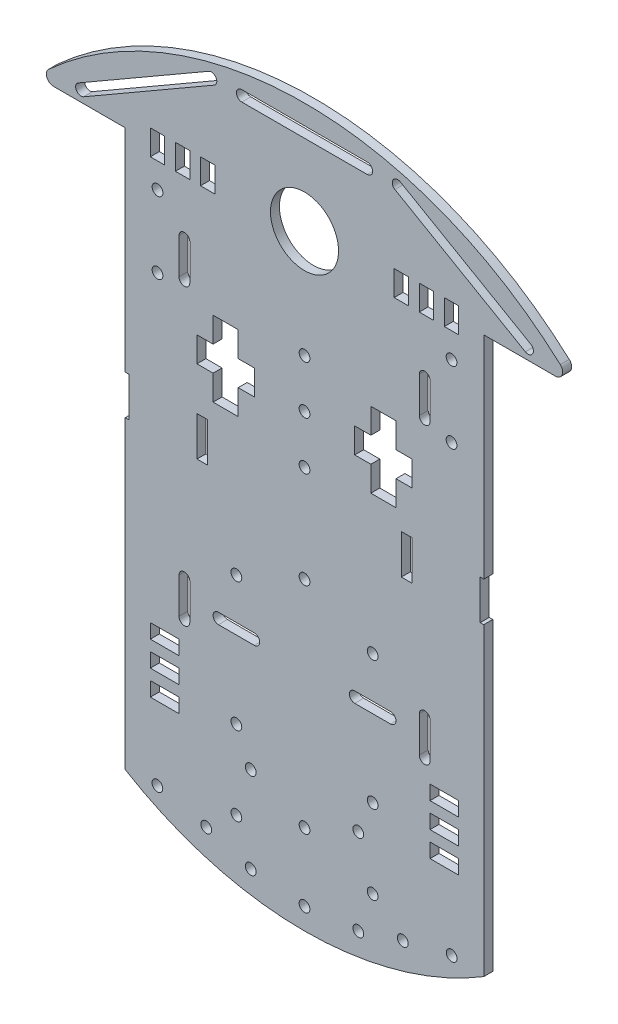
SolidWorks part; units mm, degrees
material "Acrylique (impact moyen-haut)"
ref_plane "Plan de face" through (0, 0, 0) normal (0, 0, 1) x (1, 0, 0)
ref_plane "Plan de dessus" through (0, 0, 0) normal (0, 1, 0) x (1, 0, 0)
ref_plane "Plan de droite" through (0, 0, 0) normal (1, 0, 0) x (0, 0, -1)
sketch "Esquisse1" plane through (0, 0, 0) normal (0, 0, 1) x (1, 0, 0)
  line L0 (100, 155) -> (119.9942, 155)
  line L1 (100, 77.5) -> (0, 77.5) construction
  line L2 (0, 0) -> (0, 155)
  line L3 (0, 155) -> (-19.9942, 155)
  line L4 (100, 0) -> (100, 155)
  line L5 (125, 155) -> (-25, 155) construction
  line L6 (125, 186) -> (-25, 186) construction
  line L7 (50, -14) -> (169.1274, -14) construction
  line L8 (50, 155) -> (50, 123.7315) construction
  arc A0 (121.3374, 158.4819) -> (-21.3374, 158.4819) centre (50, 79.7742) ccw
  arc A1 (100, 0) -> (0, 0) centre (50, 82.2857) cw
  arc A2 (-21.3374, 158.4819) -> (-19.9942, 155) centre (-19.9942, 157) ccw
  arc A3 (119.9942, 155) -> (121.3374, 158.4819) centre (119.9942, 157) ccw
  dimension "D3" = 200
  dimension "D5" = 31
  dimension "D1" = 2
  dimension "D2" = 100
  dimension "D4" = 150
  dimension "D6" = 155
extrude "Boss.-Extru.1" add sketch "Esquisse1" along normal blind 2.5 contours L4 L0 A3 A0 A2 L3 L2 A1
sketch "Esquisse2" plane through (0, 0, 0) normal (0, 0, -1) x (-1, 0, 0)
  line L0 (-100, 155) -> (0, 155) construction
  line L1 (-50, 155) -> (-50, 122.9953) construction
  circle A0 centre (-50, 155) radius 9.5
  point P6 (-50, 155)
  dimension "D1" = 19
extrude "Enlèv. mat.-Extru.1" cut sketch "Esquisse2" against normal through all
sketch "Esquisse3" plane through (0, 0, 0) normal (0, 0, -1) x (-1, 0, 0)
  line L1 (-93, 158.5) -> (-89, 158.5)
  line L2 (-93, 158.5) -> (-93, 151.5)
  line L3 (-93, 151.5) -> (-89, 151.5)
  line L4 (-89, 158.5) -> (-89, 151.5)
  line L5 (-100, 0) -> (-100, 155) construction
  line L11 (-100, 155) -> (-88.6993, 155) construction
  point P8 (-93, 155)
  dimension "D1" = 7
  dimension "D2" = 4
  dimension "D3" = 7
extrude "Enlèv. mat.-Extru.2" cut sketch "Esquisse3" against normal through all
pattern_linear "Répétition linéaire1" count 3 spacing 7 along (-1, 0, 0) of "Enlèv. mat.-Extru.2"
sketch "Esquisse4" plane through (0, 0, 0) normal (0, 0, -1) x (-1, 0, 0)
  line L0 (-75.5, 122) -> (-68.5, 122)
  line L1 (-68.5, 122) -> (-68.5, 115)
  line L2 (-68.5, 115) -> (-64, 115)
  line L3 (-64, 115) -> (-64, 108)
  line L4 (-64, 108) -> (-68.5, 108)
  line L5 (-68.5, 108) -> (-68.5, 101)
  line L6 (-68.5, 101) -> (-75.5, 101)
  line L7 (-75.5, 101) -> (-75.5, 108)
  line L8 (-75.5, 108) -> (-80, 108)
  line L9 (-80, 108) -> (-80, 115)
  line L10 (-80, 115) -> (-75.5, 115)
  line L11 (-75.5, 115) -> (-75.5, 122)
  line L12 (-100, 155) -> (-119.9942, 155) construction
  line L13 (-72, 122) -> (-72, 101) construction
  line L14 (-80, 111.5) -> (-64, 111.5) construction
  line L15 (-100, 0) -> (-100, 155) construction
  point P19 (-72, 111.5)
  point P21 (-72, 111.5)
  dimension "D1" = 47
  dimension "D2" = 7
  dimension "D3" = 16
  dimension "D4" = 21
  dimension "D5" = 7
  dimension "D6" = 20
extrude "Enlèv. mat.-Extru.3" cut sketch "Esquisse4" against normal through all
sketch "Esquisse5" plane through (0, 0, 0) normal (0, 0, -1) x (-1, 0, 0)
  line L0 (-80, 108) -> (-75.5, 108) construction
  line L1 (-80, 96) -> (-77, 96)
  line L2 (-80, 96) -> (-80, 85)
  line L3 (-80, 85) -> (-77, 85)
  line L4 (-77, 96) -> (-77, 85)
  line L5 (-100, 0) -> (-100, 155) construction
  dimension "D1" = 12
  dimension "D2" = 3
  dimension "D3" = 11
  dimension "D4" = 20
extrude "Enlèv. mat.-Extru.4" cut sketch "Esquisse5" against normal through all
pattern_linear "Répétition linéaire2" count 2 spacing 22 along (1, 0, 0) of "Enlèv. mat.-Extru.4"
sketch "Esquisse6" plane through (0, 0, 0) normal (0, 0, -1) x (-1, 0, 0)
  line L0 (-65, 17.5) -> (-65, 7.0648) construction
  line L1 (-100, 0) -> (-100, 85) construction
  line L2 (-83.5, 54.5) -> (-83.5, 44.5) construction
  line L3 (-82, 54.5) -> (-82, 44.5)
  line L4 (-85, 54.5) -> (-85, 44.5)
  line L5 (-74, 49.5) -> (-64, 49.5) construction
  line L6 (-74, 51) -> (-64, 51)
  line L7 (-74, 48) -> (-64, 48)
  line L8 (-83.5, 136.5) -> (-83.5, 126.5) construction
  line L9 (-82, 136.5) -> (-82, 126.5)
  line L10 (-85, 136.5) -> (-85, 126.5)
  line L11 (-112.3374, 158) -> (-75.9643, 179) construction
  line L12 (-113.0874, 159.299) -> (-76.7143, 180.299)
  line L13 (-111.5874, 156.701) -> (-75.2143, 177.701)
  line L14 (-112.3374, 158) -> (-68.1921, 158) construction
  line L15 (-100, 155) -> (-119.9942, 155) construction
  line L16 (-91, 151.5) -> (-91, 144.5) construction
  line L17 (-93, 151.5) -> (-89, 151.5) construction
  line L19 (-69, 49.5) -> (-69, 65.1561) construction
  line L20 (-50, 89.2969) -> (-50, -6.5) construction
  line L21 (0, 0) -> (0, 155) construction
  circle A0 centre (-91, 144.5) radius 1.5
  arc A1 (-82, 54.5) -> (-85, 54.5) centre (-83.5, 54.5) ccw
  circle A2 centre (-91, 124.5) radius 1.5
  circle A3 centre (-65, 17.5) radius 1.5
  circle A4 centre (-69, 26.5) radius 1.5
  circle A5 centre (-91.03, 0.6026) radius 1.5
  circle A6 centre (-77.4014, -2.6005) radius 1.5
  circle A7 centre (-69, 4.5) radius 1.5
  circle A8 centre (-65, -6.5) radius 1.5
  arc A9 (-85, 44.5) -> (-82, 44.5) centre (-83.5, 44.5) ccw
  arc A10 (-74, 51) -> (-74, 48) centre (-74, 49.5) ccw
  arc A11 (-64, 48) -> (-64, 51) centre (-64, 49.5) ccw
  arc A12 (-82, 136.5) -> (-85, 136.5) centre (-83.5, 136.5) ccw
  arc A13 (-85, 126.5) -> (-82, 126.5) centre (-83.5, 126.5) ccw
  arc A14 (-113.0874, 159.299) -> (-111.5874, 156.701) centre (-112.3374, 158) ccw
  arc A15 (-75.2143, 177.701) -> (-76.7143, 180.299) centre (-75.9643, 179) ccw
  circle A16 centre (-69, 62.5) radius 1.5
  point P21 (-83.5, 49.5)
  point P26 (-69, 49.5)
  point P33 (-83.5, 131.5)
  point P40 (-94.1508, 168.5)
  dimension "D1" = 3
  dimension "D2" = 3
  dimension "D3" = 3
  dimension "D4" = 3
  dimension "D5" = 3
  dimension "D6" = 3
  dimension "D7" = 3
  dimension "D10" = 3
  dimension "D11" = 3
  dimension "D28" = 3
  dimension "D8" = 24
  dimension "D9" = 15
  dimension "D12" = 3
  dimension "D13" = 3
  dimension "D14" = 3
  dimension "D15" = 15
  dimension "D16" = 8
  dimension "D17" = 10
  dimension "D18" = 10
  dimension "D19" = 10
  dimension "D20" = 42
  dimension "D21" = 3
  dimension "D22" = 9
  dimension "D23" = 30
  dimension "D24" = 7
  dimension "D25" = 15
  dimension "D26" = 20
  dimension "D27" = 72
  dimension "D29" = 11.5
  dimension "D30" = 21.5
  dimension "D31" = 137.5
  dimension "D32" = 14
  dimension "D33" = 13
  dimension "D34" = 11
  dimension "D35" = 22
  dimension "D36" = 34
extrude "Enlèv. mat.-Extru.5" cut sketch "Esquisse6" against normal through all
sketch "Esquisse7" plane through (0, 0, 0) normal (0, 0, -1) x (-1, 0, 0)
  line L0 (-100, 0) -> (-100, 85) construction
  line L5 (-93, 39) -> (-85, 39)
  line L6 (-93, 39) -> (-93, 35)
  line L7 (-93, 35) -> (-85, 35)
  line L8 (-85, 39) -> (-85, 35)
  line L9 (-93, 32) -> (-85, 32)
  line L10 (-93, 32) -> (-93, 28)
  line L11 (-93, 28) -> (-85, 28)
  line L12 (-85, 32) -> (-85, 28)
  line L13 (-93, 25) -> (-85, 25)
  line L14 (-93, 25) -> (-93, 21)
  line L15 (-93, 21) -> (-85, 21)
  line L16 (-85, 25) -> (-85, 21)
  arc A0 (-100, 0) -> (0, 0) centre (-50, 82.2857) ccw construction
  point P18 (-50, -14)
  dimension "D1" = 4
  dimension "D2" = 4
  dimension "D3" = 4
  dimension "D4" = 8
  dimension "D5" = 7
  dimension "D6" = 3
  dimension "D7" = 3
  dimension "D8" = 35
extrude "Enlèv. mat.-Extru.6" cut sketch "Esquisse7" against normal through all
ref_plane "Plan1" through (50, 0, 0) normal (1, 0, 0) x (0, 0, -1)
mirror "Symétrie1" about plane through (50, 0, 0) normal (1, 0, 0) of "Répétition linéaire2", "Enlèv. mat.-Extru.2", "Répétition linéaire1", "Enlèv. mat.-Extru.3", "Enlèv. mat.-Extru.4", "Enlèv. mat.-Extru.5", "Enlèv. mat.-Extru.6"
sketch "Esquisse8" plane through (0, 0, 0) normal (0, 0, -1) x (-1, 0, 0)
  line L0 (-67.5, 178.9806) -> (-32.5, 178.9806) construction
  line L1 (-67.5, 180.4806) -> (-32.5, 180.4806)
  line L2 (-67.5, 177.4806) -> (-32.5, 177.4806)
  line L5 (-50, 251.8346) -> (-50, 106.1266) construction
  line L6 (0, 0) -> (0, 85) construction
  line L7 (-100, 96) -> (-100, 155) construction
  line L8 (-64, 111.5) -> (-36, 111.5) construction
  line L9 (-64, 108) -> (-64, 115) construction
  line L10 (-36, 108) -> (-36, 115) construction
  arc A0 (-67.5, 180.4806) -> (-67.5, 177.4806) centre (-67.5, 178.9806) ccw
  arc A1 (-32.5, 177.4806) -> (-32.5, 180.4806) centre (-32.5, 178.9806) ccw
  circle A2 centre (-50, 111.5) radius 1.5
  circle A3 centre (-50, 125) radius 1.5
  circle A4 centre (-50, 98) radius 1.5
  circle A5 centre (-50, 71) radius 1.5
  circle A6 centre (-50, -8) radius 1.5
  circle A7 centre (-50, 11) radius 1.5
  point P2 (-50, 178.9806)
  dimension "D3" = 3
  dimension "D4" = 3
  dimension "D5" = 3
  dimension "D6" = 3
  dimension "D7" = 3
  dimension "D11" = 3
  dimension "D1" = 3
  dimension "D2" = 35
  dimension "D8" = 13.5
  dimension "D9" = 13.5
  dimension "D10" = 27
  dimension "D12" = 60
  dimension "D13" = 19
extrude "Enlèv. mat.-Extru.7" cut sketch "Esquisse8" against normal blind 10
equation "\"D2@Esquisse6\"=\"D1@Esquisse6\""
equation "\"D3@Esquisse6\"=\"D2@Esquisse6\""
equation "\"D4@Esquisse6\"=\"D2@Esquisse6\""
equation "\"D5@Esquisse6\"=\"D2@Esquisse6\""
equation "\"D6@Esquisse6\"=\"D2@Esquisse6\""
equation "\"D7@Esquisse6\"=\"D2@Esquisse6\""
equation "\"D2@Esquisse7\"=\"D1@Esquisse7\""
equation "\"D3@Esquisse7\"=\"D1@Esquisse7\""
equation "\"D10@Esquisse6\"=\"D7@Esquisse6\""
equation "\"D12@Esquisse6\"=\"D11@Esquisse6\""
equation "\"D13@Esquisse6\"=\"D11@Esquisse6\""
equation "\"D14@Esquisse6\"=\"D11@Esquisse6\""
equation "\"D17@Esquisse6\"=\"D19@Esquisse6\""
equation "\"D18@Esquisse6\"=\"D19@Esquisse6\""
equation "\"D28@Esquisse6\"=\"D1@Esquisse6\""
equation "\"D4@Esquisse8\"=\"D3@Esquisse8\""
equation "\"D5@Esquisse8\"=\"D3@Esquisse8\""
equation "\"D6@Esquisse8\"=\"D3@Esquisse8\""
equation "\"D7@Esquisse8\"=\"D3@Esquisse8\""
equation "\"D11@Esquisse8\"=\"D6@Esquisse8\""
